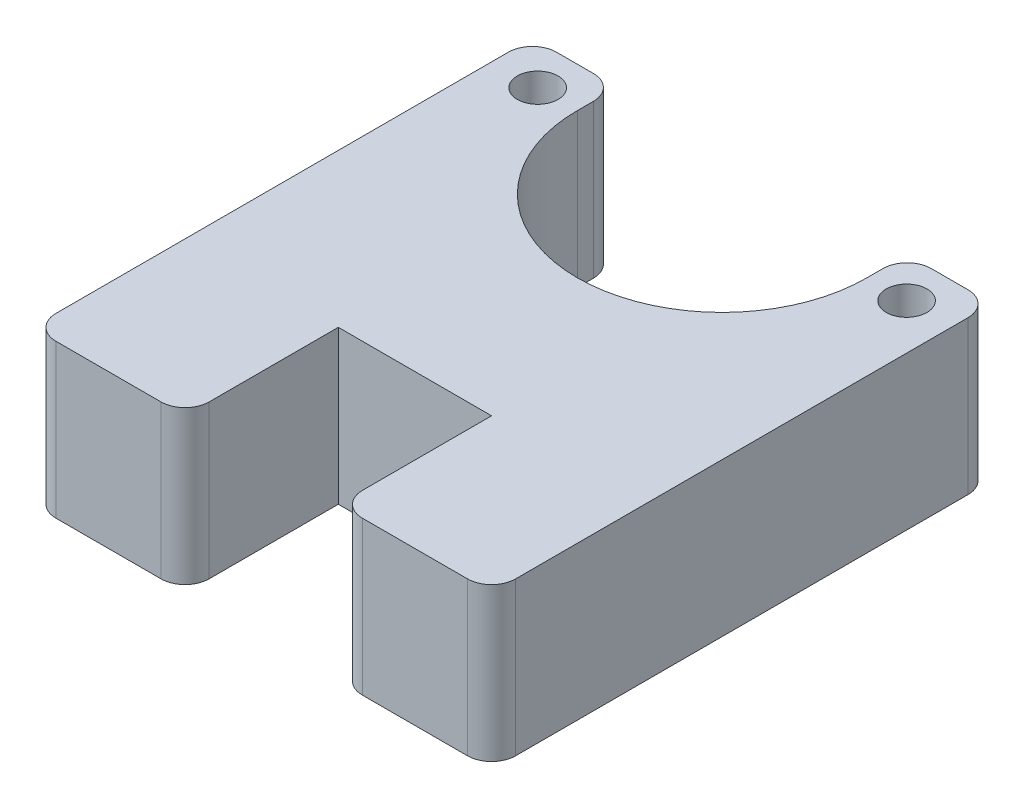
SolidWorks part; units mm, degrees
ref_plane "Front Plane" through (0, 0, 0) normal (0, 0, 1) x (1, 0, 0)
ref_plane "Top Plane" through (0, 0, 0) normal (0, 1, 0) x (1, 0, 0)
ref_plane "Right Plane" through (0, 0, 0) normal (1, 0, 0) x (0, 0, -1)
sketch "Sketch1" plane through (0, 0, 0) normal (0, 1, 0) x (1, 0, 0)
  line L0 (0, 0) -> (0, 6.0001)
  line L1 (0, 0) -> (19.05, 0)
  line L2 (0, 6.0001) -> (19.05, 6.0001)
  line L3 (19.05, 0) -> (19.05, 6.0001)
  line L4 (0, 6.0001) -> (0, 14.3937)
  line L5 (0, 6.0001) -> (3.525, 6.0001)
  line L6 (0, 14.3937) -> (3.525, 14.3937)
  line L7 (3.525, 6.0001) -> (3.525, 14.3937)
  line L8 (19.05, 6.0001) -> (19.05, 14.3937)
  line L9 (19.05, 6.0001) -> (15.525, 6.0001)
  line L10 (19.05, 14.3937) -> (15.525, 14.3937)
  line L11 (15.525, 6.0001) -> (15.525, 14.3937)
  line L12 (0, 0) -> (6.35, 0)
  line L13 (0, 0) -> (0, -6.35)
  line L14 (6.35, 0) -> (6.35, -6.35)
  line L15 (0, -6.35) -> (6.35, -6.35)
  line L16 (19.05, 0) -> (12.7, 0)
  line L17 (19.05, 0) -> (19.05, -6.35)
  line L18 (12.7, 0) -> (12.7, -6.35)
  line L19 (19.05, -6.35) -> (12.7, -6.35)
  arc A0 (3.525, 12.7287) -> (15.525, 12.7287) centre (9.525, 12.7287) ccw
  circle A1 centre (17.1675, 12.7287) radius 0.845
  circle A2 centre (1.8825, 12.7287) radius 0.845
  point P8 (9.525, 6.0001)
  dimension "D6" = 1.69
  dimension "D1" = 6.0001
  dimension "D2" = 6.35
  dimension "D3" = 6.7286
  dimension "D4" = 6
  dimension "D5" = 1.665
  dimension "D7" = 1.6425
  dimension "D9" = 6.35
  dimension "D10" = 6.35
  dimension "D11" = 6.35
  dimension "D12" = 6.35
  dimension "D13" = 1.6425
extrude "Boss-Extrude1" add sketch "Sketch1" along normal blind 6.35 contours L2 L7 L6 L4 A2 | A0 L7 L2 L11 | L11 L2 L8 L10 A1 | L1 L3 L2 L0 | L13 L15 L14 L1 | L19 L17 L1 L18 region at (9.525, 0, -3) region at (3.175, 0, 3.175) region at (1.7527, 0, -9.9892) region at (3.6626, 0, -9.3644) region at (15.875, 0, 3.175) region at (17.2973, 0, -9.9892)
fillet "Fillet3" radius 1 8 edges at (19.05, 3.175, 6.35) (12.7, 3.175, 6.35) (6.35, 3.175, 6.35) (0, 3.175, 6.35) (19.05, 3.175, -14.3937) (15.525, 3.175, -14.3937) (3.525, 3.175, -14.3937) (0, 3.175, -14.3937)
equation "\"vigorwidth\"= 0.472441in"
equation "\"vigorflangewidth\"= 0.731102in"
equation "\"vigorflangelength\"= 0.131102in"
equation "\"vigorscrewsize\"= 0.066535in"
equation "\"vigorholeoffsetwid\"= 0.0646653in"
equation "\"vigorholeoffsetlen\"= 0.065551in"
equation "\"vigorflangedepth\"= 0.0901575in"
equation "\"vigordiscdepth\"= 0.0492126in"
equation "\"vigormotordepth\"= 1.12362in"
equation "\"vigortipdepth\"= 0.259055in"
equation "\"vigoraxlewidth\"= 0.173622in"
equation "\"vigorcutlen\"= 0.0480315in"
equation "\"vigoraxledepth\"= 0.159055in"
equation "\"D4@Sketch1\"=\"vigorwidth\"/2"
equation "\"TriggerRackOffset\"=.236224in"
equation "\"D1@Sketch1\" = \"TriggerRackOffset\""
equation "\"TriggerSlotSizeInt\"=.25in"
equation "\"D10@Sketch1\" = \"TriggerSlotSizeInt\""
equation "\"D9@Sketch1\" = \"TriggerSlotSizeInt\""
equation "\"MotorMountLegLength\"=.25in"
equation "\"D11@Sketch1\"=\"MotorMountLegLength\""
equation "\"D12@Sketch1\"=\"MotorMountLegLength\""
equation "\"GearOffset\"=.264907in"
equation "\"D3@Sketch1\"=\"GearOffset\""
equation "\"D7@Sketch1\"=\"vigorholeoffsetwid\""
equation "\"D13@Sketch1\"=\"vigorholeoffsetwid\""
equation "\"D5@Sketch1\"=\"vigorflangelength\"/2"
equation "\"TriggerSlotSpacing\"=.25in"
equation "\"D2@Sketch1\" = \"TriggerSlotSpacing\""
equation "\"D6@Sketch1\"=\"vigorscrewsize\""
equation "\"CageLeftBottomEdge\"=21.15mm"
equation "\"CageLeftTopEdge\"=22.11mm"
equation "\"CageRightBottomEdge\"=21.20mm"
equation "\"CageRightTopEdge\"=21.63mm"
equation "\"CageHeight\"=86.04mm"
equation "\"CageLength\"=73.76mm"
equation "\"CageTopScrewClearance\"=10mm"
equation "\"CageBottomScrewClearance\"=25mm"
equation "\"CageLeftTopDepth\"= 11.65mm"
equation "\"CageLeftBottomDepth\"=10.15mm"
equation "\"CageLeftTopHeight\"=10.56175mm"
equation "\"CageLeftBottomHeight\"=16mm"
equation "\"CageRightTopDepth\"= 11.15mm"
equation "\"CageRightBottomDepth\"=10.15mm"
equation "\"CageRightTopHeight\"=9.775mm"
equation "\"CageRightBottomHeight\"=15.49mm"
equation "\"CageLeftTopChannelDepth\"=2.41908mm"
equation "\"CageLeftBottomChannelDepth\"=2.588mm"
equation "\"CageLeftChannelHeight\"=11.7mm"
equation "\"CageRightTopChannelDepth\"=2.59mm"
equation "\"CageRightBottomChannelDepth\"=2.318mm"
equation "\"CageRightChannelHeight\"=10mm"
equation "\"CageChanRelHeight\"=23.99mm"
equation "\"CageChanRelDepth\"=5.492mm"
equation "\"CageChamberRadius\"=16.261mm"
equation "\"CageScrewDiameter\"=4.8mm"
equation "\"CageSetScrewDiameter\"=3.5mm"
equation "\"CageAxleRadius\"=6.639mm"
equation "\"CageAxleKeyHeight\"=1.619mm"
equation "\"CageAxleKeyWidth\"=2.662mm"
equation "\"CageHoseWindowWidth\"=16.29mm"
equation "\"CageHoseWindowHeight\"=26.5mm"
equation "\"CageHoseWindow-Edge\"=8.89mm"
equation "\"CageScrew-VerticalEdge\"=5.0mm"
equation "\"CageScrew-HorizontalEdge\"=7.5mm"
equation "\"CageScrew-HoseCornerScrewEdge\"=4.45mm"
equation "\"CageAxle-BottomEdge\"=56.05mm"
equation "\"CageAxle-FrontEdge\"=46.03mm"
equation "\"CageBackSetScrew-Axle\"=40mm"
equation "\"CageFrontSetScrew-Axle\"=22mm"
equation "\"CageVelocityWindow-BackEdge\"=34.8mm"
equation "\"CageVelocityWindow-BottomEdge\"=27.55mm"
equation "\"CageVelocityWindowHeight\"=22.29mm"
equation "\"CageVelocityWindowWidth\"=12.61mm"
equation "\"TriggerSlot-BottomEdge\"=6.35mm"
equation "\"TriggerSlot-FrontEdge\"=15mm"
equation "\"TriggerSlotSize\"=6.7mm"
